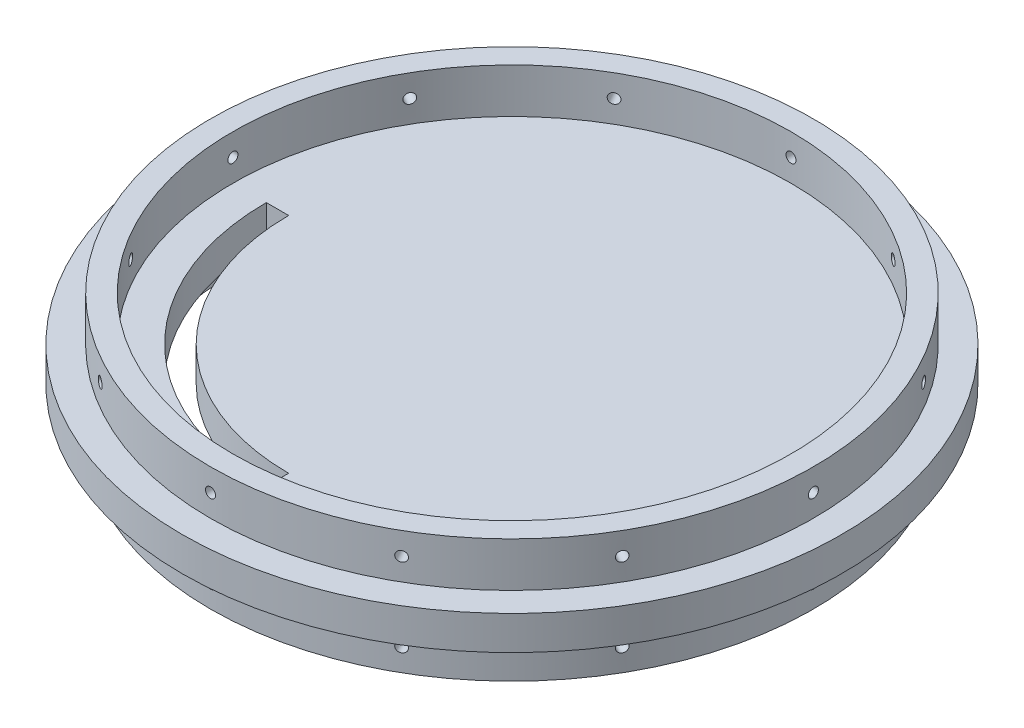
SolidWorks part; units mm, degrees
material "6061-T6 (SS)"
ref_plane "Front Plane" through (0, 0, 0) normal (0, 0, 1) x (1, 0, 0)
ref_plane "Top Plane" through (0, 0, 0) normal (0, 1, 0) x (1, 0, 0)
ref_plane "Right Plane" through (0, 0, 0) normal (1, 0, 0) x (0, 0, -1)
sketch "Sketch1" plane through (0, 0, 0) normal (0, 1, 0) x (1, 0, 0)
  circle A0 centre (0, 0) radius 93.726
  dimension "D1" = 187.452
extrude "Boss-Extrude1" add sketch "Sketch1" along normal mid plane 9.652
sketch "Sketch2" plane through (0, 0, 0) normal (0, 0, 1) x (1, 0, 0)
  line L0 (0, -18.3275) -> (0, 20.8308) construction
  line L1 (0, -4.826) -> (-19.297, -4.826)
  line L2 (-93.726, -4.826) -> (93.726, -4.826) construction
  line L3 (0, -4.826) -> (0, -1.4952)
  line L4 (-0.3818, -1.4952) -> (0, -1.4952)
  arc A0 (-19.297, -4.826) -> (-0.3818, -1.4952) centre (-0.4072, -56.7254) cw
  dimension "D6" = 55.2302
  dimension "D1" = 19.297
  dimension "D2" = 3.3308
  dimension "D3" = 0.3818
revolve "Cut-Revolve1" cut sketch "Sketch2" angle 360 about L0
sketch "Sketch4" plane through (0, 4.826, 0) normal (0, 1, 0) x (1, 0, 0)
  circle A0 centre (0, 0) radius 85.725
  circle A1 centre (0, 0) radius 79.375
  dimension "D1" = 171.45
  dimension "D2" = 158.75
extrude "Boss-Extrude2" add sketch "Sketch4" along normal blind 12.7
ref_plane "Plane1" through (0, 0, -85.725) normal (0, 0, -1) x (-1, 0, 0)
sketch "Sketch5" plane through (0, 0, -85.725) normal (0, 0, -1) x (-1, 0, 0)
  line L0 (0, 19.2786) -> (0, -19.2786) construction
  line L1 (79.375, 17.526) -> (-79.375, 17.526) construction
  circle A0 centre (0, 11.176) radius 1.4351
  dimension "D1" = 2.8702
  dimension "D2" = 6.35
extrude "Cut-Extrude2" cut sketch "Sketch5" against normal blind 12.7
pattern_circular "CirPattern1" count 12 over 360 about axis through (0, 17.526, 0) along (0, -1, 0) of "Cut-Extrude2" reverse direction yes
mirror "Mirror2" about plane through (0, 0, 0) normal (0, 1, 0) of "CirPattern1", "Cut-Extrude2", "Boss-Extrude2"
sketch "Sketch6" plane through (0, 4.826, 0) normal (0, 1, 0) x (1, 0, 0)
  line L0 (-63.5, 0) -> (-69.85, 0)
  line L1 (0, -69.85) -> (0, -63.5)
  line L2 (0, -19.2786) -> (0, 19.2786) construction
  arc A0 (-69.85, 0) -> (0, -69.85) centre (0, 0) ccw
  arc A1 (-63.5, 0) -> (0, -63.5) centre (0, 0) ccw
  dimension "D1" = 69.85
  dimension "D2" = 63.5
  dimension "D3" = 90
extrude "Cut-Extrude3" cut sketch "Sketch6" against normal up to surface (9.652 mm away) up to face at (0, -4.826, -19.297)
